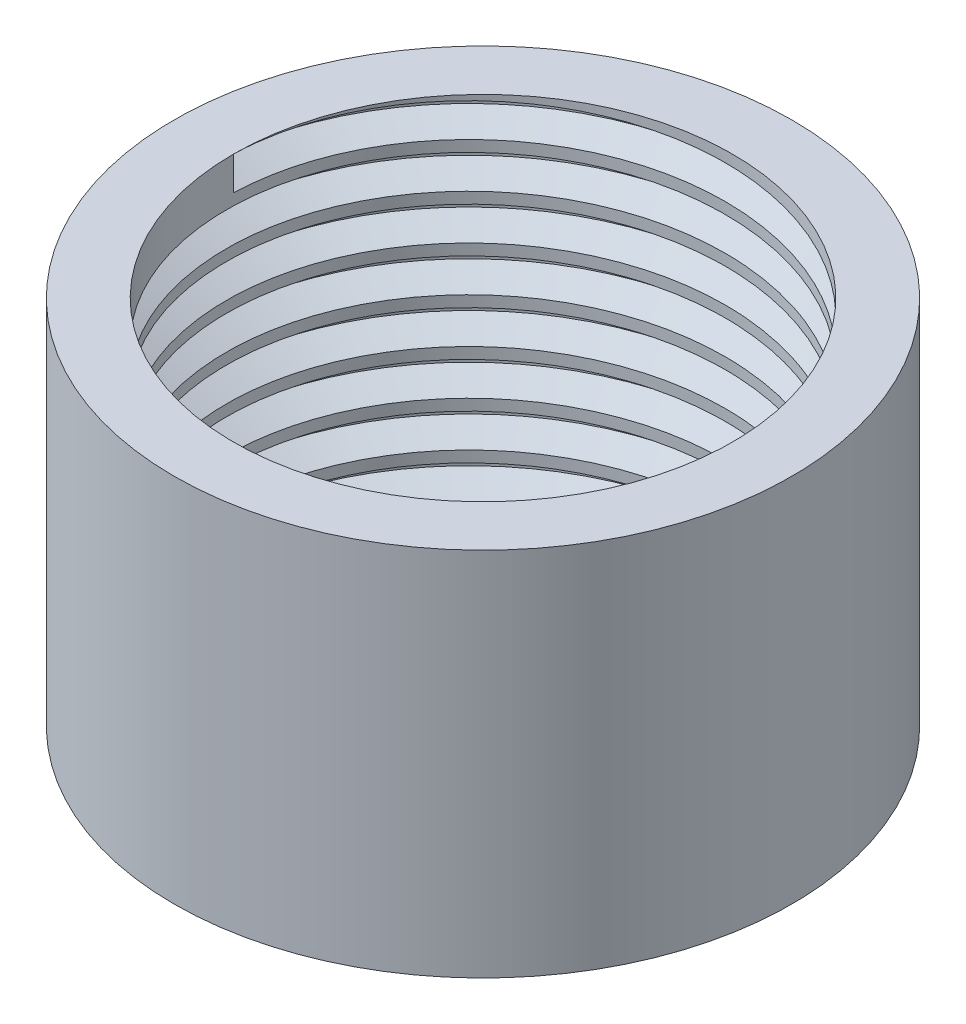
SolidWorks part; units mm, degrees
ref_plane "Front" through (0, 0, 0) normal (0, 0, 1) x (1, 0, 0)
ref_plane "Top" through (0, 0, 0) normal (0, 1, 0) x (1, 0, 0)
ref_plane "Right" through (0, 0, 0) normal (1, 0, 0) x (0, 0, -1)
sketch "Sketch1" plane through (0, 0, 0) normal (0, 1, 0) x (1, 0, 0)
  circle A0 centre (0, 0) radius 12.5
  dimension "D1" = 25
extrude "Boss-Extrude1" add sketch "Sketch1" along normal blind 15
sketch "Sketch2" plane through (0, 15, 0) normal (0, 1, 0) x (1, 0, 0)
  circle A0 centre (0, 0) radius 10.1
  dimension "D1" = 20.2
extrude "Cut-Extrude1" cut sketch "Sketch2" against normal through all
thread "Thread1" pitch 1.8143 method cut profile "Thread Profile1" start angle 0, offset 0, length 0, pitch 1.8143, diameter 20.2
ref_plane "Plane1" through (-10.1, 15, 0) normal (0, 0, 1) x (-1, 0, 0)
sketch "Thread Profile1" plane through (-10.1, 15, 0) normal (0, 0, 1) x (-1, 0, 0)
  line L0 (0, 0) -> (0, 1.8143) construction
  line L1 (0, 0) -> (0.982, 0.567)
  line L2 (0.982, 0.567) -> (0.982, 0.7937)
  line L3 (0.982, 0.7937) -> (0, 1.3607)
  line L4 (0.982, 0.6804) -> (0, 0.6804) construction
  line L11 (0, 0) -> (0, 1.3607)
  point P2 (0, 0)
  dimension "Pitch" = 1.8143
  dimension "Profile_Angle" = 60
  dimension "Profile_Land" = 0.2268
  dimension "Profile_Height" = 0.982
